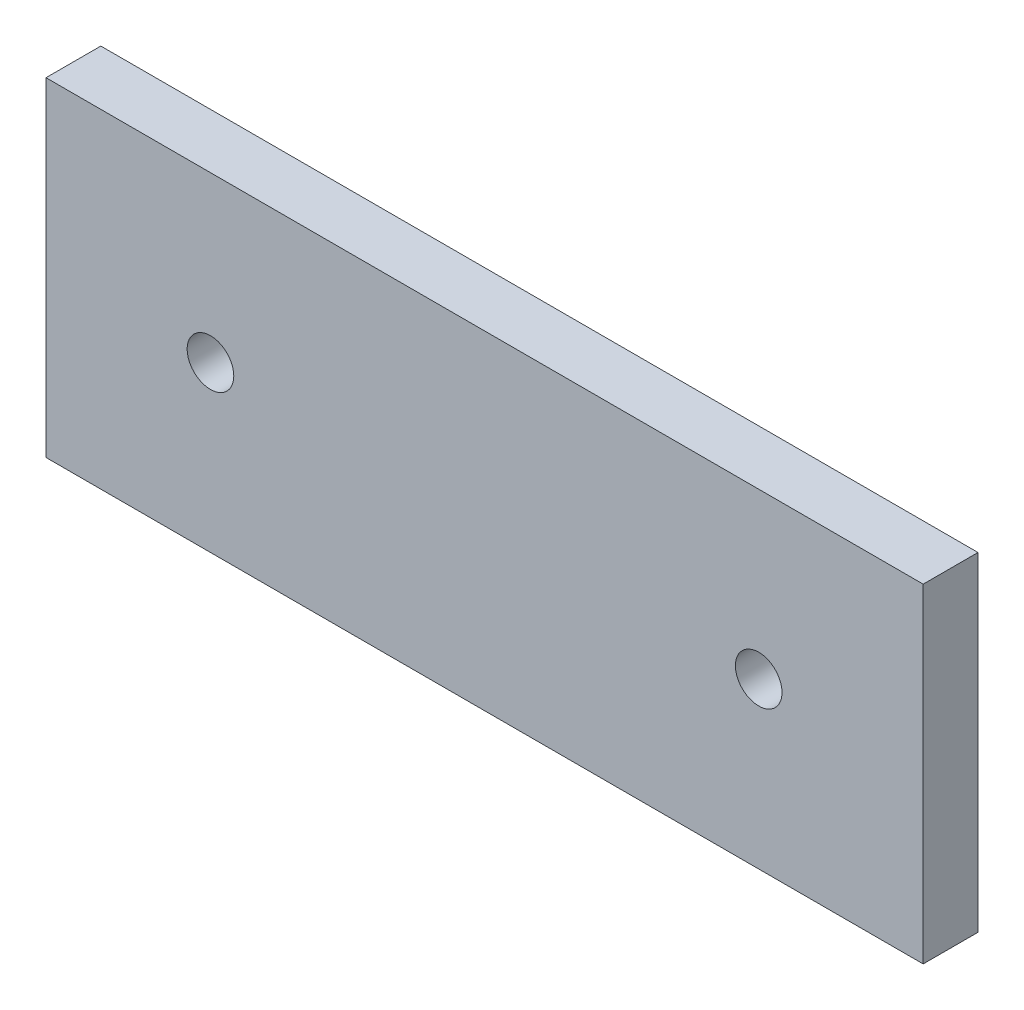
SolidWorks part; units mm, degrees
ref_plane "前视基准面" through (0, 0, 0) normal (0, 0, 1) x (1, 0, 0)
ref_plane "上视基准面" through (0, 0, 0) normal (0, 1, 0) x (1, 0, 0)
ref_plane "右视基准面" through (0, 0, 0) normal (1, 0, 0) x (0, 0, -1)
other "Configuration Table"
sketch "草图1" plane through (0, 0, 0) normal (0, 0, 1) x (1, 0, 0)
  line L1 (-12, -12) -> (52, -12)
  line L2 (-12, -12) -> (-12, 12)
  line L3 (-12, 12) -> (52, 12)
  line L4 (52, -12) -> (52, 12)
  line L5 (-12, -12) -> (52, 12) construction
  line L6 (-12, 12) -> (52, -12) construction
  circle A0 centre (0, 0) radius 1.7
  circle A1 centre (40, 0) radius 1.7
extrude "凸台-拉伸1" add sketch "草图1" along normal mid plane 4
